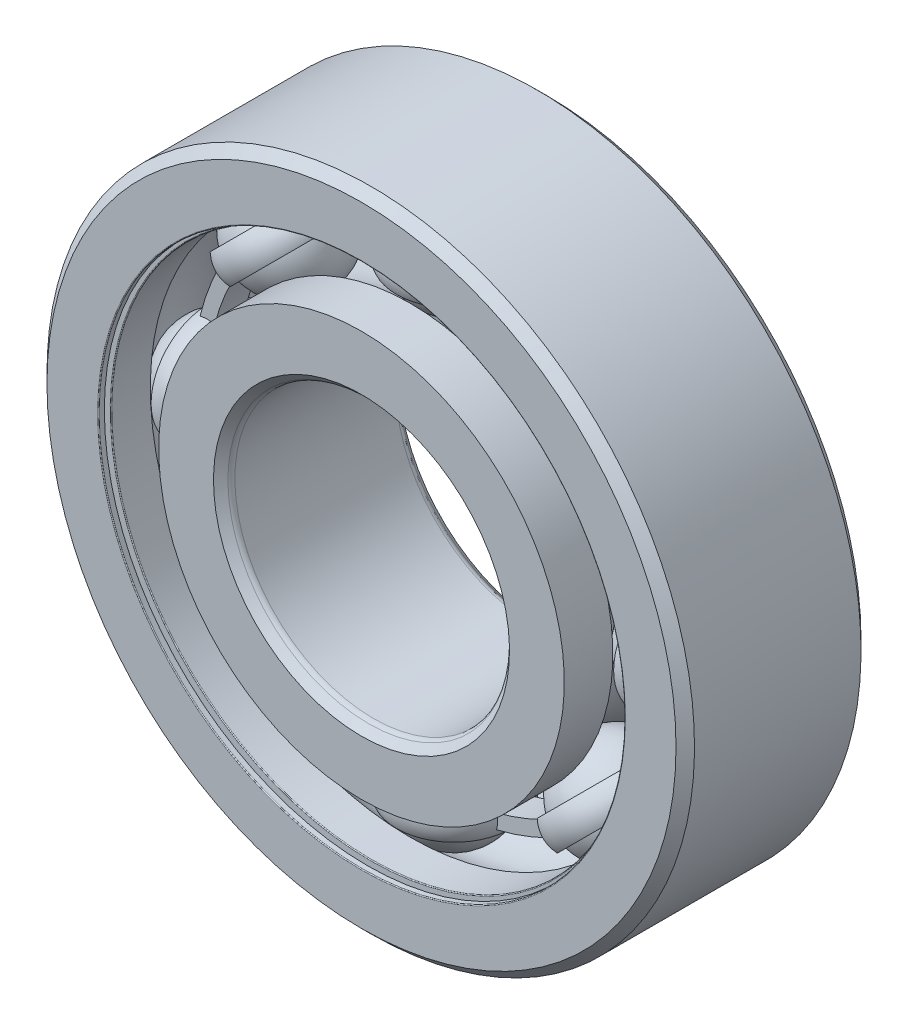
SolidWorks part; units mm, degrees
material "AISI 1035 Steel (SS)"
ref_plane "Front Plane" through (0, 0, 0) normal (0, 0, 1) x (1, 0, 0)
ref_plane "Top Plane" through (0, 0, 0) normal (0, 1, 0) x (1, 0, 0)
ref_plane "Right Plane" through (0, 0, 0) normal (1, 0, 0) x (0, 0, -1)
sketch "Sketch1" plane through (0, 0, 0) normal (0, 0, 1) x (1, 0, 0)
  line L0 (-14, 0) -> (14, 0) construction
  line L1 (-6, 0) -> (6, 0) construction
  circle A0 centre (0, 0) radius 6 construction
  circle A1 centre (0, 0) radius 14 construction
  point P3 (0, 0)
  point P6 (0, 0)
  point P7 (0, -6)
  point P11 (0, -14)
  point P12 (0, 6)
  point P13 (0, 14)
  dimension "OD" = 28
  dimension "ID" = 12
sketch "Sketch2" plane through (0, 0, 0) normal (1, 0, 0) x (0, 0, -1)
  line L0 (-4, 14) -> (4, 14) construction
  line L1 (0, 14) -> (0, -14) construction
  line L2 (3.6, 14) -> (-3.6, 14)
  line L3 (-3.6, 14) -> (-4, 13.6)
  line L4 (-4, 13.6) -> (-4, 11.2308)
  line L5 (-4, 11.2308) -> (-1.9, 11.2308)
  line L6 (4, 11.2308) -> (1.9, 11.2308)
  line L7 (4, 13.6) -> (4, 11.2308)
  line L8 (3.6, 14) -> (4, 13.6)
  line L9 (0, 14) -> (0, 10) construction
  line L10 (0, 10) -> (0, 6) construction
  line L11 (0, 14) -> (0, -14) construction
  line L12 (-4, 0) -> (4, 0) construction
  line L13 (4, 6) -> (-4, 6) construction
  line L14 (0, 12.2638) -> (0, 7.7362) construction
  line L15 (-4, -6) -> (4, -6) construction
  line L16 (-4, -6) -> (-4, 6) construction
  line L17 (4, 14) -> (4, -14) construction
  arc A0 (-1.9, 11.2308) -> (1.9, 11.2308) centre (0, 10) cw
  circle A1 centre (0, 10) radius 2.2638 construction
  point P14 (0, 6)
  point P17 (0, 0)
  point P21 (0, 14)
  point P29 (0, 6)
  point P30 (0, -6)
  point P35 (0, 12.2638)
  dimension "Approx. Ball Dia." = 4.5276
  dimension "Width" = 8
  dimension "D1" = 45
  dimension "D2" = 0.4
  dimension "D3" = 3.8
  dimension "D4" = 1.2308
  dimension "For Shaft Diameter" = 12
  dimension "For Housing ID" = 28
sketch "Sketch3" plane through (0, 0, 0) normal (1, 0, 0) x (0, 0, -1)
  line L0 (3.6, 14) -> (4, 13.6) construction
  line L1 (4, 13.6) -> (4, 11.2308) construction
  line L2 (4, 11.2308) -> (1.9, 11.2308) construction
  line L3 (-4, 11.2308) -> (-1.9, 11.2308) construction
  line L4 (-4, 13.6) -> (-4, 11.2308) construction
  line L5 (-3.6, 14) -> (-4, 13.6) construction
  line L6 (3.6, 14) -> (-3.6, 14) construction
  line L7 (3.6, 14) -> (4, 13.6)
  line L8 (4, 13.6) -> (4, 11.2308)
  line L9 (4, 11.2308) -> (1.9, 11.2308)
  line L10 (-4, 11.2308) -> (-1.9, 11.2308)
  line L11 (-4, 13.6) -> (-4, 11.2308)
  line L12 (-3.6, 14) -> (-4, 13.6)
  line L13 (3.6, 14) -> (-3.6, 14)
  arc A0 (1.9, 11.2308) -> (-1.9, 11.2308) centre (0, 10) ccw construction
  arc A1 (1.9, 11.2308) -> (-1.9, 11.2308) centre (0, 10) ccw
revolve "Revolve1" add sketch "Sketch3" angle 360 about L12
sketch "Sketch8" plane through (0, 0, 0) normal (1, 0, 0) x (0, 0, -1)
  line L0 (-4, 11.2308) -> (-1.9, 11.2308) construction
  line L1 (-3.744, 11.2308) -> (-3.6, 11.2308)
  line L2 (-3.744, 11.2308) -> (-3.744, 12.1538) construction
  line L3 (-3.744, 12.1538) -> (-3.6, 12.1538)
  line L4 (-3.6, 11.2308) -> (-3.6, 12.1538)
  line L5 (4, 11.2308) -> (1.9, 11.2308) construction
  line L6 (3.6, 11.2308) -> (3.744, 11.2308)
  line L7 (3.6, 11.2308) -> (3.6, 12.1538)
  line L8 (3.6, 12.1538) -> (3.744, 12.1538)
  line L9 (3.744, 11.2308) -> (3.744, 12.1538) construction
  line L10 (-3.6, 12.1538) -> (3.6, 12.1538) construction
  line L11 (0, 14) -> (0, -14) construction
  line L12 (-3.744, 12.1538) -> (-3.744, 13.0769) construction
  line L13 (-3.744, 13.0769) -> (-3.744, 14) construction
  line L14 (-4, 14) -> (4, 14) construction
  line L15 (-3.744, 11.2308) -> (-4, 11.2308)
  line L16 (-4, 11.2308) -> (-4, 11.3748)
  line L17 (-4, 13.6) -> (-4, 11.2308) construction
  line L18 (-4, 11.3748) -> (-3.744, 11.3748)
  line L19 (-3.744, 11.3748) -> (-3.744, 12.1538)
  line L20 (3.744, 11.2308) -> (4, 11.2308)
  line L21 (4, 11.2308) -> (4, 11.3748)
  line L22 (4, 13.6) -> (4, 11.2308) construction
  line L23 (4, 11.3748) -> (3.744, 11.3748)
  line L24 (3.744, 11.3748) -> (3.744, 12.1538)
  point P12 (0, 12.1538)
  dimension "D1" = 7.2
  dimension "D2" = 0.144
revolve "Cut-Revolve1" cut sketch "Sketch8" angle 360 about L12
sketch "Sketch4" plane through (0, 0, 0) normal (1, 0, 0) x (0, 0, -1)
  line L0 (0, 14) -> (0, -14) construction
  line L1 (0, 14) -> (0, -14) construction
  line L2 (-3.6, 6) -> (-4, 6.4)
  line L3 (-4, 6.4) -> (-4, 8.7692)
  line L5 (-4, 8.7692) -> (-1.9, 8.7692)
  line L6 (-3.6, 6) -> (3.6, 6)
  line L8 (3.6, 6) -> (4, 6.4)
  line L10 (4, 6.4) -> (4, 8.7692)
  line L11 (4, 8.7692) -> (1.9, 8.7692)
  line L12 (-4, 13.6) -> (-4, 11.2308) construction
  line L13 (3.6, 14) -> (4, 13.6) construction
  line L15 (4, -13.6) -> (4, 13.6) construction
  line L16 (3.6, 14) -> (3.6, -14) construction
  arc A1 (1.9, 8.7692) -> (-1.9, 8.7692) centre (0, 10) cw
  circle A2 centre (0, 10) radius 2.2638 construction
  point P1 (0, 6)
revolve "Revolve2" add sketch "Sketch4" angle 360 about L12
sketch "Sketch5" plane through (0, 0, 0) normal (1, 0, 0) x (0, 0, -1)
  line L0 (-2.2638, 10) -> (2.2638, 10)
  arc A2 (-2.2638, 10) -> (2.2638, 10) centre (0, 10) cw
  arc A3 (1.9, 11.2308) -> (-1.9, 11.2308) centre (0, 10) ccw construction
revolve "Revolve3" add sketch "Sketch5" angle 360 about L0
sketch "Sketch6" plane through (0, 0, 0) normal (1, 0, 0) x (0, 0, -1)
  line L0 (-1.9, 11.2308) -> (-1.9, 10.6154) construction
  line L1 (-1.9, 10.6154) -> (-1.9, 10) construction
  line L2 (-1.9, 10) -> (-1.9, 9.3846) construction
  line L3 (-1.9, 9.3846) -> (-1.9, 8.7692) construction
  line L4 (-4, 10.6154) -> (-3.6964, 10.6154) construction
  line L5 (-1.9, 10.6154) -> (-1.9, 9.3846) construction
  line L7 (-3.6964, 10.6154) -> (-3.3929, 10.6154) construction
  line L8 (-3.3929, 10.6154) -> (-3.0893, 10.6154) construction
  line L10 (0, 14) -> (0, -14) construction
  line L11 (0, 14) -> (0, -14) construction
  line L12 (-4, 11.2308) -> (-4, 10.6154) construction
  line L13 (-2.4821, 10.6154) -> (-2.1786, 10.6154) construction
  line L14 (-4, 13.6) -> (-4, -13.6) construction
  line L15 (-4, 10.6154) -> (-4, 10) construction
  line L16 (-4, 10) -> (-4, 9.3846) construction
  line L17 (-4, 9.3846) -> (-4, 8.7692) construction
  line L18 (-3.0893, 10.6154) -> (-2.7857, 10.6154) construction
  line L19 (-2.7857, 10.6154) -> (-2.4821, 10.6154) construction
  line L20 (-2.1786, 10.6154) -> (-2.4821, 10.6154)
  line L21 (-4, 9.3846) -> (-3.6964, 9.3846) construction
  line L22 (-3.6964, 9.3846) -> (-3.3929, 9.3846) construction
  line L23 (-3.3929, 9.3846) -> (-3.0893, 9.3846) construction
  line L24 (-3.0893, 9.3846) -> (-2.7857, 9.3846) construction
  line L25 (-2.7857, 9.3846) -> (-2.4821, 9.3846) construction
  line L26 (-2.4821, 9.3846) -> (-2.1786, 9.3846) construction
  line L27 (-2.1786, 9.3846) -> (-2.4821, 9.3846)
  line L28 (-2.7857, 10.6154) -> (-2.7857, 9.3846) construction
  line L30 (-2.6339, 10.6154) -> (-2.6339, 9.3846) construction
  circle A0 centre (0, 10) radius 2.2638 construction
  arc A2 (-2.4821, 9.3846) -> (-2.4821, 10.6154) centre (-1.3106, 10) cw
  arc A3 (-2.1786, 10.6154) -> (-2.1786, 9.3846) centre (0, 10) ccw
revolve "Revolve4" add sketch "Sketch6" angle 360 about L11
sketch "Sketch7" plane through (0, 0, 0) normal (0, 0, 1) x (1, 0, 0)
  line L0 (-2.2638, 10) -> (2.2638, 10) construction
  line L1 (0, 7.7362) -> (0, 12.2638) construction
  line L2 (0, 0) -> (3.8268, 9.2388) construction
  line L8 (0, 14) -> (0, -14) construction
  line L9 (7.0711, 7.0711) -> (7.5062, 7.5062)
  line L10 (0, 14) -> (0, -14) construction
  line L11 (0, 10.6154) -> (0, 10)
  arc A1 (7.0711, 7.0711) -> (0, 10) centre (0, 0) ccw
  arc A2 (7.5062, 7.5062) -> (0, 10.6154) centre (0, 0) ccw
  dimension "D1" = 45
  dimension "D2" = 4.5276
extrude "Boss-Extrude1" add sketch "Sketch7" along normal mid plane 1.3333
pattern_circular "CirPattern1" count 8 over 360 about axis through (0, 0, 4) along (0, 0, -1) of bodies 104 134
pattern_circular "CirPattern2" count 8 over 360 about axis through (0, 0, 4) along (0, 0, -1) of "Revolve4", "Boss-Extrude1" reverse direction yes
fillet "Fillet1" radius 0.036 4 edges at (0, -11.2308, -3.6) (0, -11.3748, -4) (0, -11.2308, 3.6) (0, -11.3748, 4)
fillet "Fillet2" radius 0.3 2 edges at (0, -6, -3.6) (0, -6, 3.6)
ref_plane "Plane1" through (3.8268, 9.2388, 0) normal (0.3827, 0.9239, 0) x (0.9239, -0.3827, 0)
sketch "Sketch9" plane through (3.8268, 9.2388, 0) normal (0.3827, 0.9239, 0) x (0.9239, -0.3827, 0)
  line L0 (-1.7354, -0.6667) -> (-1.7354, -2)
  line L1 (-1.7354, -2) -> (-0.7527, -2)
  line L2 (-0.7527, -2) -> (0, -1.3684)
  line L3 (0, -1.3684) -> (0.7527, -2)
  line L4 (0.7527, -2) -> (1.7354, -2)
  line L5 (1.7354, -2) -> (1.7354, -0.6667)
  line L6 (1.7354, -0.6667) -> (-1.7354, -0.6667)
  line L7 (0, -0.6667) -> (0, 0) construction
  line L8 (-1.7354, -0.6667) -> (-1.7354, 0) construction
  dimension "D1" = 1.3333
  dimension "D2" = 0.6667
  dimension "D3" = 40
extrude "Boss-Extrude2" [suppressed] add sketch "Sketch9" along normal blind 1.9808 draft 15 and the other way blind 1.9808 draft 10 separate body draft outward yes other way draft outward yes
fillet "Fillet3" [suppressed] radius 0.4
mirror "Mirror1" [suppressed] about plane through (0, 0, 0) normal (0, 0, 1) of bodies 149
pattern_circular "CirPattern3" [suppressed] count 8 over 360 about axis through (0, 0, 4) along (0, 0, -1) of bodies 158 149
equation "\"D2@Sketch2\" = \"Width@Sketch2\" * .05"
equation "\"D3@Sketch2\"=\"Width@Sketch2\" * .475"
equation "\"D4@Sketch2\" =  (  (  ( \"OD@Sketch1\" - \"Width@Sketch2\" )  / 2 )  / 3.25 )  / 2.5"
equation "\"D1@Boss-Extrude1\" = \"Width@Sketch2\" / 6"
equation "\"D1@Sketch8\"=\"Width@Sketch2\"*.9"
equation "\"D2@Sketch8\"=\"D1@Sketch8\"*.02"
equation "\"D1@Fillet1\" = \"D2@Sketch8\" * .25"
equation "\"D1@Fillet2\" = \"D2@Sketch2\" * .75"
equation "\"Approx No of Balls@CirPattern1\" = ( pi * \"OD@Sketch1\" ) * .4 / \"Approx. Ball Dia.@Sketch2\""
equation "\"D1@Sketch7\" = 360 / \"Approx No of Balls@CirPattern1\""
equation "\"D1@CirPattern2\" = \"Approx No of Balls@CirPattern1\""
equation "\"D2@Sketch7\"=\"Approx. Ball Dia.@Sketch2\""
equation "\"D2@Sketch9\" = \"D1@Boss-Extrude1\" * .5"
equation "\"D1@Sketch9\"=\"D2@Sketch9\"*2"
equation "\"D1@Boss-Extrude2\"=\"Approx. Ball Dia.@Sketch2\"*.4375"
equation "\"D2@Boss-Extrude2\"=\"D1@Boss-Extrude2\""
equation "\"D1@CirPattern3\" = \"Approx No of Balls@CirPattern1\""
equation "\"D1@Fillet3\"=\"D1@Sketch9\" * .3"
